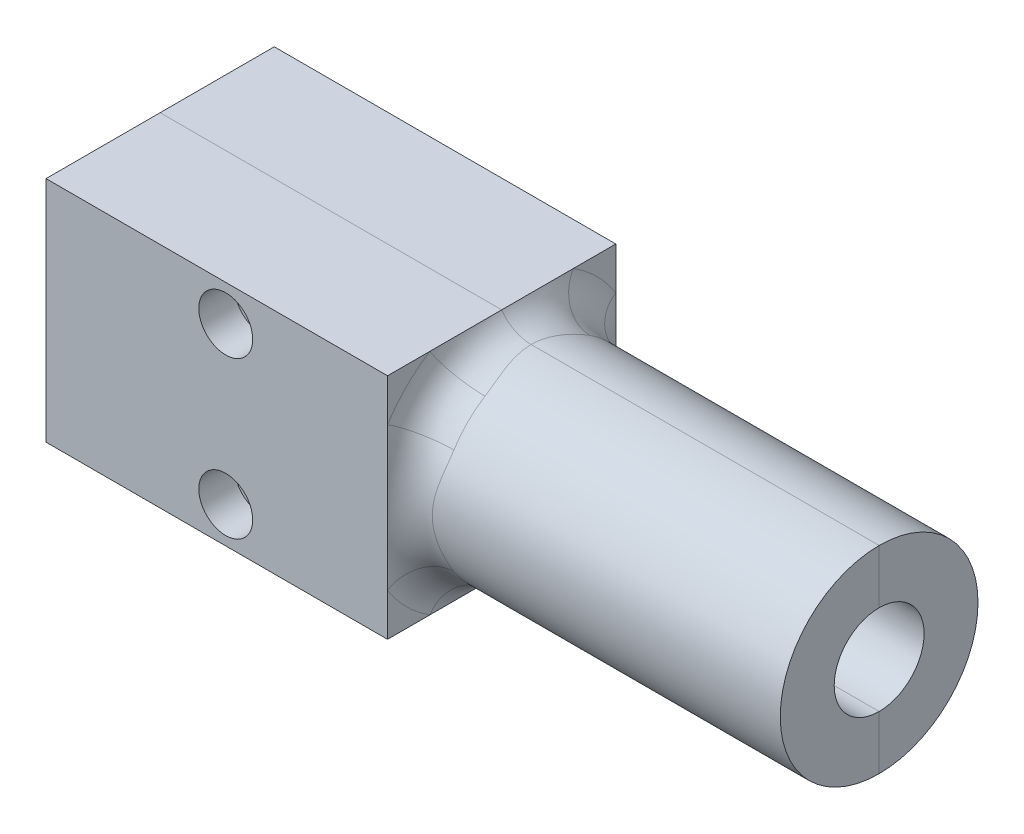
SolidWorks part; units mm, degrees
material "PLA"
ref_plane "Ebene vorne" through (0, 0, 0) normal (1, 0, 0) x (0, 1, 0)
ref_plane "Ebene oben" through (0, 0, 0) normal (0, 0, 1) x (0, 1, 0)
ref_plane "Ebene rechts" through (0, 0, 0) normal (0, 1, 0) x (-1, 0, 0)
sketch "Skizze5" plane through (0, 0, 0) normal (1, 0, 0) x (0, 1, 0)
  line L1 (-12.7, -12.7) -> (12.7, -12.7)
  line L2 (-12.7, -12.7) -> (-12.7, 12.7)
  line L3 (-12.7, 12.7) -> (12.7, 12.7)
  line L4 (12.7, -12.7) -> (12.7, 12.7)
  line L5 (-12.7, -12.7) -> (12.7, 12.7) construction
  line L6 (-12.7, 12.7) -> (12.7, -12.7) construction
  point P0 (0, 0)
  dimension "D1" = 25.4
  dimension "D2" = 25.4
extrude "Motorarm" add sketch "Skizze5" along normal blind 60 and the other way blind 20
sketch "Skizze6" plane through (60, 0, 0) normal (1, 0, 0) x (0, 1, 0)
  circle A0 centre (0, 0) radius 5
  dimension "D1" = 10
extrude "Welle" cut sketch "Skizze6" against normal blind 80
sketch "Skizze7" plane through (-20, 0, 0) normal (-1, 0, 0) x (0, -1, 0)
  line L5 (-8.5, -8.5) -> (8.5, 8.5) construction
  line L6 (-8.5, 8.5) -> (8.5, -8.5) construction
  circle A0 centre (-8.5, 8.5) radius 2
  circle A1 centre (8.5, 8.5) radius 2
  circle A2 centre (-8.5, -8.5) radius 2
  circle A3 centre (8.5, -8.5) radius 2
  point P0 (0, 0)
  dimension "D1" = 17
  dimension "D2" = 17
extrude "Löcher AS5600" cut sketch "Skizze7" against normal blind 7
sketch "Skizze9" plane through (0, 0, -12.7) normal (0, 0, -1) x (1, 0, 0)
  line L8 (0, 9.5) -> (-8.2272, 4.75) construction
  line L9 (-8.2272, 4.75) -> (-8.2272, -4.75) construction
  line L10 (-8.2272, -4.75) -> (0, -9.5) construction
  line L11 (0, -9.5) -> (8.2272, -4.75) construction
  line L12 (8.2272, -4.75) -> (8.2272, 4.75) construction
  line L13 (8.2272, 4.75) -> (0, 9.5) construction
  circle A4 centre (0, 0) radius 8.2272 construction
  circle A6 centre (8.2272, 4.75) radius 2
  circle A7 centre (8.2272, -4.75) radius 2
  circle A9 centre (-8.2272, -4.75) radius 2
  circle A10 centre (-8.2272, 4.75) radius 2
extrude "Löcher Motoraufnahme" cut sketch "Skizze9" against normal blind 7
sketch "Skizze10" plane through (0, 0, 0) normal (1, 0, 0) x (0, 1, 0)
  circle A0 centre (0, 0) radius 8.2
  dimension "D1" = 16.4
extrude "Kugellager 1" cut sketch "Skizze10" along normal blind 5.3 from offset 12
sketch "Skizze11" plane through (0, 0, 0) normal (1, 0, 0) x (0, 1, 0)
  circle A0 centre (0, 0) radius 8.2
  dimension "D1" = 16.4
extrude "Kugellager 2" cut sketch "Skizze11" along normal blind 5.3 from offset 40
sketch "Skizze12" plane through (0, 0, 0) normal (1, 0, 0) x (0, 1, 0)
  circle A1 centre (0, 0) radius 11
  dimension "D1" = 22
extrude "Materialreduzierung" cut sketch "Skizze12" along normal blind 42 from offset 18 flip side to cut
sketch "Skizze14" plane through (0, 0, -12.7) normal (0, 0, -1) x (1, 0, 0)
  line L15 (18, 12.7) -> (0, 12.7) construction
  line L16 (18, 12.7) -> (18, 8.7) construction
  line L17 (18, 8.7) -> (0, 8.7) construction
  line L18 (0, 12.7) -> (0, 8.7) construction
  line L19 (3.3, 8.7) -> (1.65, 11.5579)
  line L20 (1.65, 11.5579) -> (-1.65, 11.5579)
  line L21 (-1.65, 11.5579) -> (-3.3, 8.7)
  line L22 (-3.3, 8.7) -> (-1.65, 5.8421)
  line L23 (-1.65, 5.8421) -> (1.65, 5.8421)
  line L24 (1.65, 5.8421) -> (3.3, 8.7)
  line L25 (18, -12.7) -> (0, -12.7) construction
  line L26 (18, -12.7) -> (18, -8.7) construction
  line L27 (18, -8.7) -> (0, -8.7) construction
  line L28 (0, -12.7) -> (0, -8.7) construction
  line L29 (3.3, -8.7) -> (1.65, -5.8421)
  line L30 (1.65, -5.8421) -> (-1.65, -5.8421)
  line L31 (-1.65, -5.8421) -> (-3.3, -8.7)
  line L32 (-3.3, -8.7) -> (-1.65, -11.5579)
  line L33 (-1.65, -11.5579) -> (1.65, -11.5579)
  line L34 (1.65, -11.5579) -> (3.3, -8.7)
  circle A0 centre (0, 8.7) radius 3.3 construction
  circle A1 centre (0, 8.7) radius 2.8579 construction
  circle A2 centre (0, -8.7) radius 3.3 construction
  circle A3 centre (0, -8.7) radius 2.8579 construction
  dimension "D3" = 18
  dimension "D1" = 18
  dimension "D2" = 4
  dimension "D4" = 4
extrude "Platz für Muttern" cut sketch "Skizze14" against normal blind 3
sketch "Skizze17" plane through (0, 0, -12.7) normal (0, 0, -1) x (1, 0, 0)
  circle A0 centre (0, -8.7) radius 3.3 construction
  circle A1 centre (0, -8.7) radius 1.65
  circle A2 centre (0, 8.7) radius 3.3 construction
  circle A3 centre (0, 8.7) radius 1.65
  dimension "D1" = 3.3
extrude "Platz für Stange" cut sketch "Skizze17" against normal blind 25.4
sketch "Skizze18" plane through (0, 0, 12.7) normal (0, 0, 1) x (1, 0, 0)
  circle A0 centre (0, 8.7) radius 3
  circle A1 centre (0, -8.7) radius 3
  dimension "D1" = 6
extrude "Platz für Schraubenkopf" cut sketch "Skizze18" against normal blind 4
sketch "Skizze21" plane through (0, 0, 0) normal (0, 0, 1) x (0, 1, 0)
  line L0 (-11, -60) -> (11, -60) construction
  line L1 (-12.7, 20) -> (-8.7, 20) construction
  line L2 (-12.7, 20) -> (-12.7, 10) construction
  line L3 (-12.7, 10) -> (-8.7, 10) construction
  line L4 (-8.7, 20) -> (-8.7, 10) construction
  line L5 (12.7, 20) -> (8.7, 20) construction
  line L6 (12.7, 20) -> (12.7, 10) construction
  line L7 (12.7, 10) -> (8.7, 10) construction
  line L8 (8.7, 20) -> (8.7, 10) construction
  line L9 (9, -60) -> (7, -60) construction
  line L10 (9, -60) -> (9, -54) construction
  line L11 (9, -54) -> (7, -54) construction
  line L12 (7, -60) -> (7, -54) construction
  line L14 (-9, -60) -> (-7, -60) construction
  line L15 (-9, -60) -> (-9, -54) construction
  line L16 (-9, -54) -> (-7, -54) construction
  line L17 (-7, -60) -> (-7, -54) construction
  circle A0 centre (-8.7, 10) radius 0.7
  circle A1 centre (8.7, 10) radius 0.7
  circle A2 centre (-7, -54) radius 0.7
  circle A3 centre (7, -54) radius 0.7
  dimension "D9" = 1.4
  dimension "D1" = 6
  dimension "D2" = 2
  dimension "D3" = 6
  dimension "D4" = 2
  dimension "D5" = 10
  dimension "D6" = 4
  dimension "D7" = 4
  dimension "D8" = 10
extrude "Platz für Fixierung" cut sketch "Skizze21" against normal blind 2.5 and the other way blind 2.5
fillet "Verrundung2" radius 4 1 edges at (18, 0, -11)
split "Abspalten1" trim tools "Ebene oben" bodies to split 115 resulting bodies 116 117
sketch "Skizze24" plane through (0, 0, -12.7) normal (0, 0, -1) x (1, 0, 0)
  line L1 (8.2272, 4.75) -> (0, 9.5) construction
  line L2 (0, 9.5) -> (-8.2272, 4.75) construction
  line L3 (-8.2272, 4.75) -> (-8.2272, -4.75) construction
  line L4 (-8.2272, -4.75) -> (0, -9.5) construction
  line L5 (0, -9.5) -> (8.2272, -4.75) construction
  line L6 (8.2272, -4.75) -> (8.2272, 4.75) construction
  circle A0 centre (0, 0) radius 8.2272 construction
  circle A1 centre (-8.2272, 4.75) radius 3
  circle A2 centre (8.2272, 4.75) radius 3
  circle A3 centre (-8.2272, -4.75) radius 3
  circle A4 centre (8.2272, -4.75) radius 3
extrude "Schnitt-Linear austragen1" cut sketch "Skizze24" against normal blind 1
